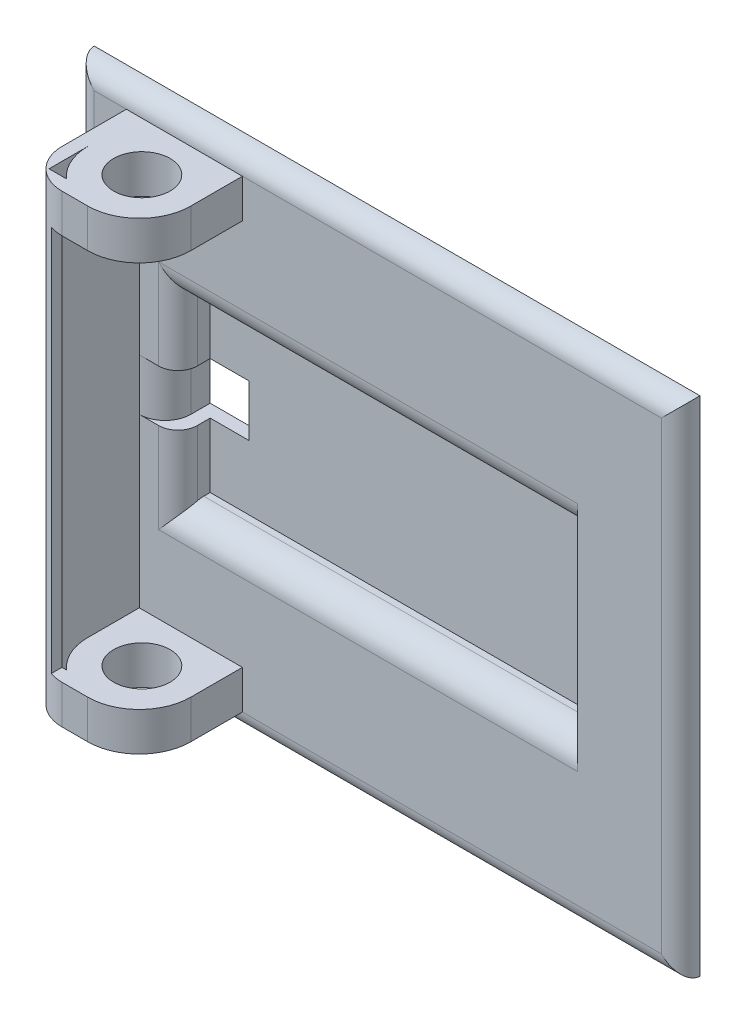
SolidWorks part; units mm, degrees
ref_plane "Plan de face" through (0, 0, 0) normal (0, 0, 1) x (1, 0, 0)
ref_plane "Plan de dessus" through (0, 0, 0) normal (0, 1, 0) x (1, 0, 0)
ref_plane "Plan de droite" through (0, 0, 0) normal (1, 0, 0) x (0, 0, -1)
sketch "Esquisse1" plane through (0, 0, 0) normal (0, 0, 1) x (1, 0, 0)
  line L1 (0, 0) -> (47, 0)
  line L2 (0, 0) -> (0, 39)
  line L3 (0, 39) -> (47, 39)
  line L4 (47, 0) -> (47, 39)
  dimension "D1" = 47
  dimension "D2" = 39
extrude "Boss.-Extru.1" add sketch "Esquisse1" along normal blind 2.5
sketch "Esquisse2" plane through (0, 0, 2.5) normal (0, 0, 1) x (1, 0, 0)
  line L0 (0, 39) -> (0, 0) construction
  line L1 (5, 37.5) -> (13, 37.5)
  line L2 (5, 37.5) -> (5, 34.5)
  line L3 (5, 34.5) -> (13, 34.5)
  line L4 (13, 37.5) -> (13, 34.5)
  line L5 (5, 4.5) -> (13, 4.5)
  line L6 (5, 4.5) -> (5, 1.5)
  line L7 (5, 1.5) -> (13, 1.5)
  line L8 (13, 4.5) -> (13, 1.5)
  line L9 (47, 39) -> (0, 39) construction
  point P8 (9, 37.5)
  point P11 (9, 4.5)
  point P12 (9, 34.5)
  point P13 (5, 36)
  point P14 (5, 3)
  dimension "D1" = 9
  dimension "D2" = 0
  dimension "D3" = 8
  dimension "D4" = 8
  dimension "D5" = 3
  dimension "D6" = 3
  dimension "D7" = 33
  dimension "D8" = 3
extrude "Boss.-Extru.2" add sketch "Esquisse2" along normal blind 8
sketch "Esquisse3" plane through (0, 1.5, 0) normal (0, -1, 0) x (1, 0, 0)
  line L0 (5, 10.5) -> (13, 10.5) construction
  circle A0 centre (9, 6.3) radius 2.192
  point P4 (9, 10.5)
  dimension "D1" = 0
  dimension "D2" = 4.2
extrude "Enlèv. mat.-Extru.1" cut sketch "Esquisse3" against normal through all
fillet "Congé1" radius 4 4 edges at (13, 3, 10.5) (5, 3, 10.5) (13, 36, 10.5) (5, 36, 10.5)
sketch "Esquisse4" plane through (0, 0, 2.5) normal (0, 0, 1) x (1, 0, 0)
  line L0 (0, 39) -> (0, 0) construction
  line L1 (8, 26.5) -> (39, 26.5)
  line L2 (8, 26.5) -> (8, 12.5)
  line L3 (8, 12.5) -> (39, 12.5)
  line L4 (39, 26.5) -> (39, 12.5)
  point P6 (0, 19.5)
  point P7 (8, 19.5)
  dimension "D1" = 8
  dimension "D2" = 31
  dimension "D3" = 0
  dimension "D4" = 14
extrude "Enlèv. mat.-Extru.2" cut sketch "Esquisse4" against normal blind 20
fillet "Congé2" radius 2 2 edges at (23.5, 26.5, 2.5) (23.5, 12.5, 2.5)
sketch "Esquisse5" plane through (0, 0, 2.5) normal (0, 0, 1) x (1, 0, 0)
  line L1 (5, 34.5) -> (6.5, 34.5)
  line L2 (5, 34.5) -> (5, 7.1704)
  line L3 (5, 7.1704) -> (6.5, 7.1704)
  line L4 (6.5, 34.5) -> (6.5, 7.1704)
  dimension "D1" = 1.5
extrude "Boss.-Extru.3" [suppressed] add sketch "Esquisse5" along normal blind 5
sketch "Esquisse6" plane through (0, 0, 2.5) normal (0, 0, 1) x (1, 0, 0)
  line L0 (5, 37.5) -> (5, 34.5) construction
  line L1 (5, 39.3123) -> (13, 39.3123)
  line L2 (5, 39.3123) -> (5, 1.5)
  line L3 (5, 1.5) -> (13, 1.5)
  line L4 (13, 39.3123) -> (13, 1.5)
extrude "Boss.-Extru.4" [suppressed] add sketch "Esquisse6" along normal blind 10
fillet "Congé3" [suppressed] radius 4
sketch "Esquisse7" plane through (0, 0, 0) normal (0, 0, -1) x (-1, 0, 0)
  line L0 (-39, 10.5) -> (-39, 28.5) construction
  line L1 (-4.1119, 34.5) -> (-16.5781, 34.5)
  line L2 (-4.1119, 34.5) -> (-4.1119, 4.5)
  line L3 (-4.1119, 4.5) -> (-16.5781, 4.5)
  line L4 (-16.5781, 34.5) -> (-16.5781, 4.5)
  point P4 (-16.5781, 19.5)
  point P7 (-39, 19.5)
  dimension "D1" = 0
  dimension "D2" = 30
extrude "Enlèv. mat.-Extru.3" [suppressed] cut sketch "Esquisse7" against normal blind 18 from vertex
sketch "Esquisse8" plane through (0, 0, 2.5) normal (0, 0, 1) x (1, 0, 0)
  line L0 (5, 37.5) -> (5, 34.5) construction
  line L1 (4, 37.5) -> (5, 37.5)
  line L2 (4, 37.5) -> (4, 1.5)
  line L3 (4, 1.5) -> (5, 1.5)
  line L4 (5, 37.5) -> (5, 1.5)
  line L5 (13, 37.5) -> (5, 37.5) construction
  line L6 (5, 1.5) -> (13, 1.5) construction
  point P9 (4.5, 1.5)
  dimension "D1" = 0
  dimension "D2" = 0
  dimension "D3" = 0
  dimension "D4" = 1
extrude "Boss.-Extru.5" add sketch "Esquisse8" along normal blind 8
sketch "Esquisse9" plane through (5, 0, 0) normal (1, 0, 0) x (0, 0, -1)
  line L0 (-10.5, 37.5) -> (-6.5, 37.5) construction
  line L1 (-10.5, 1.5) -> (-9.5, 1.5)
  line L2 (-10.5, 1.5) -> (-10.5, 37.5)
  line L3 (-10.5, 37.5) -> (-9.5, 37.5)
  line L4 (-9.5, 1.5) -> (-9.5, 37.5)
  dimension "D1" = 1
extrude "Boss.-Extru.6" add sketch "Esquisse9" along normal blind 4
sketch "Esquisse10" plane through (0, 0, 10.5) normal (0, 0, 1) x (1, 0, 0)
  line L1 (6, 34.5) -> (13.4493, 34.5)
  line L2 (6, 34.5) -> (6, 4.5)
  line L3 (6, 4.5) -> (13.4493, 4.5)
  line L4 (13.4493, 34.5) -> (13.4493, 4.5)
  line L5 (9, 34.5) -> (9, 4.5) construction
  line L6 (4, 37.5) -> (4, 1.5) construction
  point P6 (6, 19.5)
  point P9 (9, 19.5)
  dimension "D1" = 30
  dimension "D2" = 0
  dimension "D3" = 2
extrude "Enlèv. mat.-Extru.4" cut sketch "Esquisse10" against normal up to surface (8 mm away) up to face at (23.5, 19.5, 2.5)
fillet "Congé4" radius 3 1 edges at (4, 19.5, 10.5)
sketch "Esquisse11" plane through (0, 0, 0) normal (0, 0, -1) x (-1, 0, 0)
  line L0 (-8, 26.5) -> (-39, 26.5) construction
  line L1 (-43, 32) -> (-4, 32)
  line L2 (-43, 32) -> (-43, 7)
  line L3 (-43, 7) -> (-4, 7)
  line L4 (-4, 32) -> (-4, 7)
  line L5 (-8, 12.5) -> (-8, 26.5) construction
  point P4 (-23.5, 32)
  point P7 (-23.5, 26.5)
  point P8 (-4, 19.5)
  point P11 (-8, 19.5)
  dimension "D1" = 0
  dimension "D2" = 0
  dimension "D3" = 25
  dimension "D4" = 39
extrude "Enlèv. mat.-Extru.5" cut sketch "Esquisse11" against normal blind 1 flip side to cut
sketch "Esquisse12" plane through (0, 0, 0) normal (0, 0, -1) x (-1, 0, 0)
  line L1 (-43, 32) -> (-4, 32)
  line L2 (-43, 32) -> (-43, 7)
  line L3 (-43, 7) -> (-4, 7)
  line L4 (-4, 32) -> (-4, 7)
extrude "Boss.-Extru.7" add sketch "Esquisse12" along normal blind 1
sketch "Esquisse13" plane through (0, 0, 2.5) normal (0, 0, 1) x (1, 0, 0)
  line L0 (8, 12.5) -> (8, 26.5) construction
  line L1 (11, 17.5) -> (7, 17.5)
  line L2 (11, 17.5) -> (11, 21.5)
  line L3 (11, 21.5) -> (7, 21.5)
  line L4 (7, 17.5) -> (7, 21.5)
  line L5 (6, 34.5) -> (6, 4.5) construction
  point P4 (7, 19.5)
  point P7 (8, 19.5)
  dimension "D1" = 0
  dimension "D2" = 1
  dimension "D3" = 4
  dimension "D4" = 4
extrude "Enlèv. mat.-Extru.6" cut sketch "Esquisse13" against normal up to next
fillet "Congé6" radius 2 1 edges at (7, 19.5, 2.5)
fillet "Congé7" radius 1.5 6 edges at (8, 25, 2.5) (8, 14, 2.5) (0, 19.5, 2.5) (23.5, 0, 2.5) (47, 19.5, 2.5) (23.5, 39, 2.5)
fillet "Congé8" radius 1.5 4 edges at (4, 19.5, -1) (23.5, 7, -1) (43, 19.5, -1) (23.5, 32, -1)
